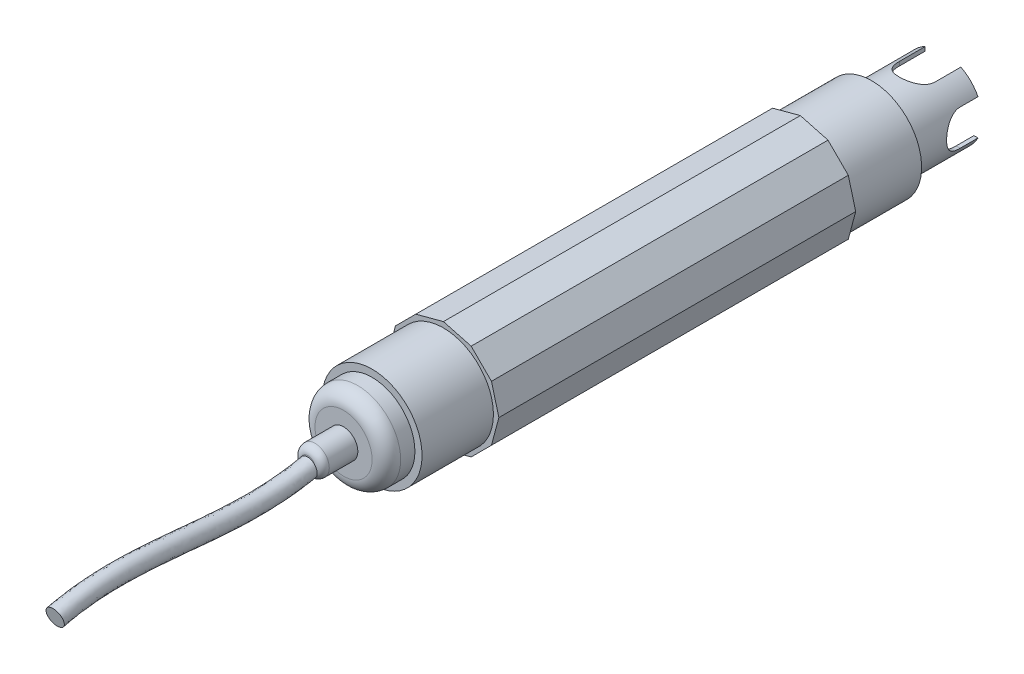
SolidWorks part; units mm, degrees
ref_plane "Front Plane" through (0, 0, 0) normal (0, 0, 1) x (1, 0, 0)
ref_plane "Top Plane" through (0, 0, 0) normal (0, 1, 0) x (1, 0, 0)
ref_plane "Right Plane" through (0, 0, 0) normal (1, 0, 0) x (0, 0, -1)
sketch "Sketch1" plane through (0, 0, 0) normal (0, 0, 1) x (1, 0, 0)
  line L0 (-15.5291, 0) -> (-13.4486, -7.7646)
  line L1 (15.5291, 0) -> (13.4486, 7.7646)
  line L2 (13.4486, 7.7646) -> (7.7646, 13.4486)
  line L3 (7.7646, 13.4486) -> (0, 15.5291)
  line L4 (0, 15.5291) -> (-7.7646, 13.4486)
  line L5 (-7.7646, 13.4486) -> (-13.4486, 7.7646)
  line L6 (-13.4486, 7.7646) -> (-15.5291, 0)
  line L7 (-13.4486, -7.7646) -> (-7.7646, -13.4486)
  line L8 (-7.7646, -13.4486) -> (0, -15.5291)
  line L9 (0, -15.5291) -> (7.7646, -13.4486)
  line L10 (7.7646, -13.4486) -> (13.4486, -7.7646)
  line L11 (13.4486, -7.7646) -> (15.5291, 0)
  circle A0 centre (0, 0) radius 15 construction
extrude "Boss-Extrude1" add sketch "Sketch1" against normal blind 100
sketch "Sketch2" plane through (0, 0, 0) normal (0, 0, 1) x (1, 0, 0)
  circle A0 centre (0, 0) radius 14
  dimension "D1" = 28
extrude "Boss-Extrude2" add sketch "Sketch2" along normal blind 20
sketch "Sketch3" plane through (0, 0, 20) normal (0, 0, 1) x (1, 0, 0)
  circle A0 centre (0, 0) radius 12
extrude "Boss-Extrude3" add sketch "Sketch3" along normal blind 8
fillet "Fillet1" radius 4 1 edges at (12, 0, 28)
sketch "Sketch4" plane through (0, 0, 28) normal (0, 0, 1) x (1, 0, 0)
  circle A0 centre (0, 0) radius 4
extrude "Boss-Extrude4" add sketch "Sketch4" along normal blind 10
fillet "Fillet2" radius 2 1 edges at (4, 0, 38)
sketch "Sketch6" plane through (0, 0, -100) normal (0, 0, -1) x (-1, 0, 0)
  circle A0 centre (0, 0) radius 14
extrude "Boss-Extrude6" add sketch "Sketch6" along normal blind 20
sketch "Sketch7" plane through (0, 0, -120) normal (0, 0, -1) x (-1, 0, 0)
  circle A0 centre (0, 0) radius 10
  circle A1 centre (0, 0) radius 11
  dimension "D1" = 1
extrude "Boss-Extrude7" add sketch "Sketch7" along normal blind 20
sketch "Sketch8" plane through (0, 0, 0) normal (1, 0, 0) x (0, 0, -1)
  line L0 (140, -11) -> (140, 11) construction
  line L1 (145, -5) -> (135, -5)
  line L2 (145, -5) -> (145, 5)
  line L3 (145, 5) -> (135, 5)
  line L5 (145, -5) -> (135, 5) construction
  line L6 (145, 5) -> (135, -5) construction
  arc A0 (135, 5) -> (135, -5) centre (135, 0) ccw
  point P0 (140, 0)
  dimension "D1" = 10
extrude "Cut-Extrude1" cut sketch "Sketch8" against normal up to next and the other way up to next
sketch "Sketch9" plane through (0, 0, 0) normal (0, 1, 0) x (1, 0, 0)
  line L0 (9.798, 140) -> (-9.798, 140) construction
  line L2 (-5, 132.7558) -> (-5, 147.2442)
  line L3 (-5, 147.2442) -> (5, 147.2442)
  line L4 (5, 132.7558) -> (5, 147.2442)
  line L5 (-5, 132.7558) -> (5, 147.2442) construction
  line L6 (-5, 147.2442) -> (5, 132.7558) construction
  arc A0 (-5, 132.7558) -> (5, 132.7558) centre (0, 132.7558) ccw
  point P0 (0, 140)
  dimension "D1" = 10
extrude "Cut-Extrude2" cut sketch "Sketch9" against normal up to next and the other way up to next
sketch "Sketch10" plane through (0, 0, -120) normal (0, 0, -1) x (-1, 0, 0)
  circle A0 centre (0, 0) radius 10
extrude "Boss-Extrude8" add sketch "Sketch10" along normal blind 8
sketch "Sketch11" plane through (0, 0, -128) normal (0, 0, -1) x (-1, 0, 0)
  circle A0 centre (0, 0) radius 3
extrude "Boss-Extrude9" add sketch "Sketch11" along normal blind 6
fillet "Fillet3" radius 3 1 edges at (-3, 0, -134)
sketch "Sketch23" plane through (0, 0, 0) normal (1, 0, 0) x (0, 0, -1)
  spline S0 degree 3 poles (-34.2183, 0) (-59.081, -6.9051) (-83.9859, 4.2525) (-108.8162, -1.8443) knots 0 0 0 0 1 1 1 1
  point P2 (-108.8162, -1.8443)
  point P4 (-81.6263, -3.0062)
  point P6 (-64.1969, 0)
  point P7 (-34.2183, 0)
  point P8 (-61.1758, -2.0767)
  point P9 (-88.1333, 0)
sweep "Sweep1" add path "Sketch23" circular profile diameter 5 parameters "D3"=5
